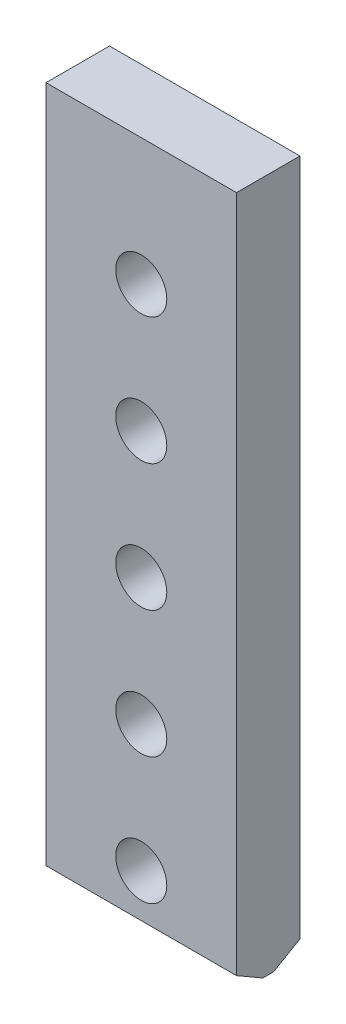
SolidWorks part; units mm, degrees
ref_plane "Спереди" through (0, 0, 0) normal (0, 0, 1) x (1, 0, 0)
ref_plane "Сверху" through (0, 0, 0) normal (0, 1, 0) x (1, 0, 0)
ref_plane "Справа" through (0, 0, 0) normal (1, 0, 0) x (0, 0, -1)
sketch "Эскиз1" plane through (0, 0, 0) normal (0, 0, 1) x (1, 0, 0)
  line L1 (0, 0) -> (75, 0)
  line L2 (0, 0) -> (0, 273)
  line L3 (0, 273) -> (75, 273)
  line L4 (75, 0) -> (75, 273)
  point P5 (37.5, 273)
  dimension "D1" = 273
  dimension "D2" = 75
extrude "Бобышка-Вытянуть1" add sketch "Эскиз1" along normal blind 25
sketch "Эскиз2" plane through (0, 0, 25) normal (0, 0, 1) x (1, 0, 0)
  line L0 (0, 0) -> (75, 0) construction
  line L1 (75, 0) -> (75, 273) construction
  circle A0 centre (37.5, 23) radius 10.05
  circle A1 centre (37.5, 73) radius 10.05
  circle A2 centre (37.5, 123) radius 10.05
  circle A3 centre (37.5, 173) radius 10.05
  circle A4 centre (37.5, 223) radius 10.05
  dimension "D1" = 5
  dimension "D2" = 23
  dimension "D3" = 37.5
  dimension "D4" = 20.1
extrude "Вырез-Вытянуть1" cut sketch "Эскиз2" against normal through all
chamfer "Фаска1" distance 6 angle 60 1 edges at (37.5, 0, 0) first distance on face at (47.55, 73, 0)
chamfer "Фаска2" distance 6 angle 60 1 edges at (37.5, 0, 25) first distance on face at (47.55, 73, 25)
